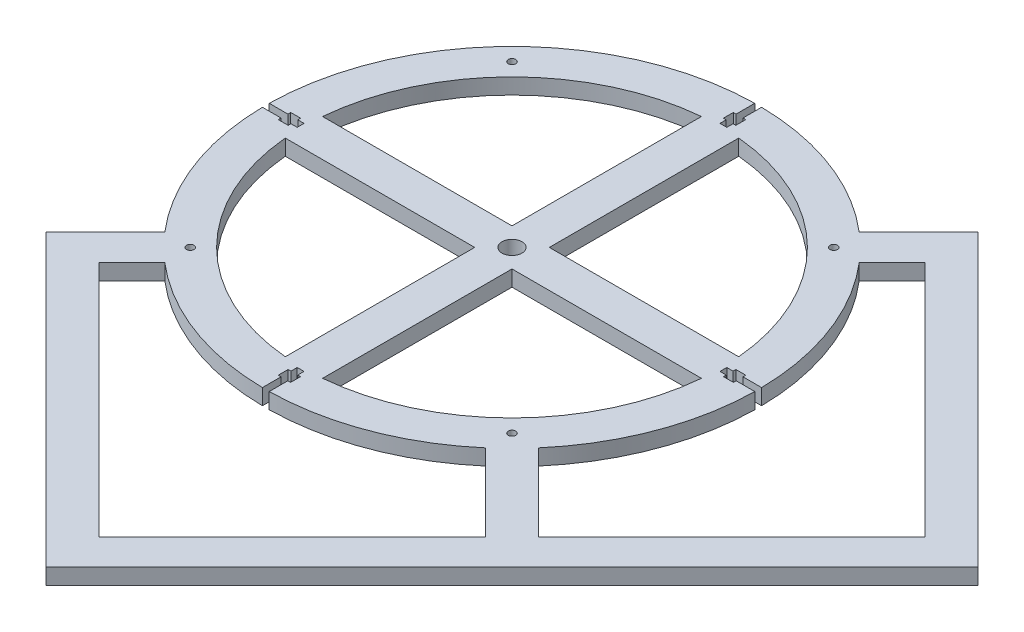
SolidWorks part; units mm, degrees
ref_plane "Front Plane" through (0, 0, 0) normal (0, 0, 1) x (1, 0, 0)
ref_plane "Top Plane" through (0, 0, 0) normal (0, 1, 0) x (1, 0, 0)
ref_plane "Right Plane" through (0, 0, 0) normal (1, 0, 0) x (0, 0, -1)
sketch "Sketch1" plane through (0, 0, 0) normal (0, 1, 0) x (1, 0, 0)
  line L0 (0, -99) -> (0, 99) construction
  line L1 (-99, 0) -> (99, 0) construction
  line L2 (-98.7155, -7.5) -> (98.7155, -7.5)
  line L3 (7.5, -98.7155) -> (7.5, 98.7155)
  line L4 (-98.7155, 7.5) -> (98.7155, 7.5)
  line L5 (-7.5, -98.7155) -> (-7.5, 98.7155)
  line L6 (-7.5, -99) -> (-7.5, 99) construction
  line L7 (7.5, -99) -> (7.5, 99) construction
  line L8 (-99, -7.5) -> (99, -7.5) construction
  line L9 (-99, 7.5) -> (99, 7.5) construction
  line L10 (-88.3883, -88.3883) -> (17.6777, -194.4544) construction
  line L11 (17.6777, -194.4544) -> (194.4544, -17.6777) construction
  line L12 (194.4544, -17.6777) -> (88.3883, 88.3883) construction
  line L13 (0, 0) -> (33755.9757, 33755.9757) construction
  line L14 (-88.3883, -88.3883) -> (-70.0036, -70.0036) construction
  line L15 (88.3883, 88.3883) -> (70.0036, 70.0036) construction
  line L16 (106.066, -106.066) -> (70.0036, -70.0036) construction
  line L17 (111.3693, -100.7627) -> (75.1057, -64.4991)
  line L18 (88.3883, 77.7817) -> (75.1057, 64.4991)
  line L19 (183.8478, -17.6777) -> (88.3883, 77.7817)
  line L20 (17.6777, -183.8478) -> (183.8478, -17.6777)
  line L21 (-77.7817, -88.3883) -> (17.6777, -183.8478)
  line L22 (-77.7817, -88.3883) -> (-64.4991, -75.1057)
  line L23 (100.7627, -111.3693) -> (64.4991, -75.1057)
  line L24 (88.3883, 98.9949) -> (64.4991, 75.1057)
  line L25 (205.061, -17.6777) -> (88.3883, 98.9949)
  line L26 (17.6777, -205.061) -> (205.061, -17.6777)
  line L27 (-98.9949, -88.3883) -> (17.6777, -205.061)
  line L28 (-98.9949, -88.3883) -> (-75.1057, -64.4991)
  line L29 (-77.7817, -88.3883) -> (-64.7003, -75.3069) construction
  line L30 (-98.9949, -88.3883) -> (-75.3069, -64.7003) construction
  line L31 (88.3883, 77.7817) -> (75.3069, 64.7003) construction
  line L32 (88.3883, 98.9949) -> (64.7003, 75.3069) construction
  line L33 (111.3693, -100.7627) -> (75.3069, -64.7003) construction
  line L34 (100.7627, -111.3693) -> (64.7003, -75.3069) construction
  circle A0 centre (0, 0) radius 100 construction
  circle A1 centre (0, 0) radius 99
  circle A2 centre (0, 0) radius 84
  point P7 (0, 0)
  point P11 (0, 0)
  dimension "D1" = 200
  dimension "D2" = 1
  dimension "D3" = 15
  dimension "D6" = 25
  dimension "D7" = 25
  dimension "D8" = 50
  dimension "D9" = 15
  dimension "D10" = 45
  dimension "D4" = 7.5
  dimension "D5" = 7.5
  dimension "D11" = 7.5
  dimension "D12" = 7.5
extrude "Boss-Extrude1" add sketch "Sketch1" along normal mid plane 6.35 contours A2 L2 A1 L5 | A2 L4 A1 L2 | A2 L5 A1 L4 | A2 L3 A1 L5 | A2 L4 A1 L3 | A2 L2 A1 L4 | A2 L3 A1 L2 | A2 L5 A1 L3 | L5 A2 L3 L2 | L4 A2 L2 L5 | L3 A2 L5 L4 | L2 A2 L4 L3 | L5 L2 L3 L4 | A1 L18 L19 L20 L21 L22 L28 L27 L26 L25 L24 | A1 L23 L20 L17 region at (-91.3966, 0, 0) region at (-59.642, 0, 59.642) region at (-45.6942, 0, 0) region at (-59.642, 0, -59.642) region at (-73.0441, 0, 73.0441) region at (0, 0, 0) region at (0, 0, 45.6942) region at (0, 0, 91.3966) region at (0, 0, -91.3966) region at (45.6942, 0, 0) region at (0, 0, -45.6942) region at (59.642, 0, 59.642) region at (59.642, 0, -59.642) region at (91.3966, 0, 0) region at (85.3496, 0, 85.3496)
sketch "Sketch2" plane through (0, 0, 0) normal (0, 1, 0) x (1, 0, 0)
  line L0 (-1.375, 85) -> (-1.375, 99)
  line L1 (-1.375, 85) -> (1.375, 85)
  line L2 (-1.375, 99) -> (1.375, 99)
  line L3 (1.375, 85) -> (1.375, 99)
  line L4 (-1.375, 85) -> (1.375, 99) construction
  line L5 (-1.375, 99) -> (1.375, 85) construction
  line L6 (-2.5, 87.5) -> (-2.5, 91.5)
  line L7 (-2.5, 87.5) -> (2.5, 87.5)
  line L8 (-2.5, 91.5) -> (2.5, 91.5)
  line L9 (2.5, 87.5) -> (2.5, 91.5)
  line L10 (-2.5, 87.5) -> (2.5, 91.5) construction
  line L11 (-2.5, 91.5) -> (2.5, 87.5) construction
  line L12 (0, -1000) -> (0, 49000) construction
  line L13 (-1000, 0) -> (49000, 0) construction
  circle A0 centre (0, 0) radius 99 construction
  point P1 (0, 92)
  point P2 (0, 89.5)
  dimension "D1" = 2.75
  dimension "D2" = 14
  dimension "D3" = 4
  dimension "D4" = 5
  dimension "D5" = 2.5
extrude "Cut-Extrude1" cut sketch "Sketch2" against normal through all both and the other way through all contours L7 L0 L1 L3 | L8 L0 L7 L3 | L7 L9 L8 L3 | L0 L8 L3 L2 | L8 L6 L7 L0 region at (0, 0, -86.25) region at (-1.9375, 0, -89.5) region at (0, 0, -89.5) region at (0, 0, -95.25) region at (1.9375, 0, -89.5)
pattern_circular "CirPattern1" count 4 over 360 about axis through (0, 3.175, 0) along (0, 1, 0) of "Cut-Extrude1"
hole_wizard "Ø3.0 (3) Diameter Hole1" positions "Sketch3" profile "Sketch4" hole size "Ø3.0" standard "ANSI Metric" end condition up to next
sketch "Sketch3" plane through (0, 3.175, 0) normal (0, 1, 0) x (1, 0, 0)
  line L0 (-70.0036, -70.0036) -> (70.0036, 70.0036) construction
  line L2 (-70.0036, 70.0036) -> (70.0036, -70.0036) construction
  line L4 (70.0036, 70.0036) -> (59.397, 59.397)
  line L6 (70.0036, -70.0036) -> (59.397, -59.397)
  line L8 (-70.0036, -70.0036) -> (-59.397, -59.397)
  line L10 (-70.0036, 70.0036) -> (-59.397, 59.397)
  arc A2 (83.6645, 7.5) -> (7.5, 83.6645) centre (0, 0) ccw construction
  arc A3 (7.5, -83.6645) -> (83.6645, -7.5) centre (0, 0) ccw construction
  arc A4 (-83.6645, -7.5) -> (-7.5, -83.6645) centre (0, 0) ccw construction
  arc A5 (-7.5, 83.6645) -> (-83.6645, 7.5) centre (0, 0) ccw construction
  circle A6 centre (0, 0) radius 99
  arc A7 (-1.375, 98.9905) -> (-98.9905, 1.375) centre (0, 0) ccw construction
  point P107 (0, 0)
  point P324 (0, 0)
  point P360 (-64.7003, 64.7003)
  point P362 (64.7003, 64.7003)
  point P364 (64.7003, -64.7003)
  point P366 (-64.7003, -64.7003)
  point P375 (-70.0036, -70.0036)
  point P376 (70.0036, -70.0036)
  point P377 (69.9625, 69.9625)
  point P378 (68.5584, 68.5584)
sketch "Sketch4" plane through (-64.7003, 3.175, 64.7003) normal (1, 0, 0) x (0, 0, 1)
  line L0 (0, 0) -> (0, 6.35)
  line L1 (0, 6.35) -> (1.5, 6.35)
  line L2 (1.5, 6.35) -> (1.5, 0)
  line L5 (1.5, 0) -> (0, 0)
  line L11 (0, -6.35) -> (0, 107.95) construction
  dimension "Thru Hole Dia." = 3
  dimension "Thru Hole Depth" = 6.35
hole_wizard "Ø8.0 (8) Diameter Hole1" positions "Sketch5" profile "Sketch6" hole size "Ø8.0" standard "ANSI Metric" end condition up to next
sketch "Sketch5" plane through (0, 3.175, 0) normal (0, 1, 0) x (1, 0, 0)
  point P0 (0, 0)
sketch "Sketch6" plane through (0, 3.175, 0) normal (1, 0, 0) x (0, 0, 1)
  line L0 (0, 0) -> (0, 6.35)
  line L1 (0, 6.35) -> (4, 6.35)
  line L2 (4, 6.35) -> (4, 0)
  line L5 (4, 0) -> (0, 0)
  line L11 (0, -6.35) -> (0, 107.95) construction
  dimension "Thru Hole Dia." = 8
  dimension "Thru Hole Depth" = 6.35
